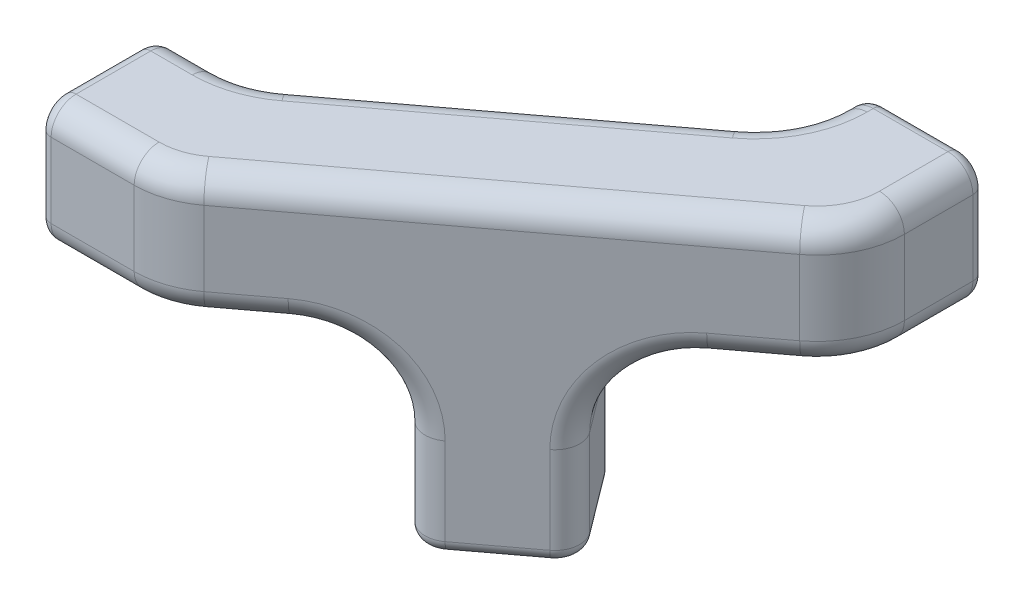
SolidWorks part; units mm, degrees
ref_plane "Front Plane" through (0, 0, 0) normal (0, 0, 1) x (1, 0, 0)
ref_plane "Top Plane" through (0, 0, 0) normal (0, 1, 0) x (1, 0, 0)
ref_plane "Right Plane" through (0, 0, 0) normal (1, 0, 0) x (0, 0, -1)
sketch "Sketch1" plane through (0, 0, 0) normal (0, 1, 0) x (1, 0, 0)
  line L0 (-103.8063, 185.5563) -> (-105.9277, 187.6777) construction
  line L1 (-108.7561, 184.8492) -> (-103.0992, 190.5061)
  line L2 (-103.0992, 190.5061) -> (-100.7186, 188.1255)
  line L3 (-100.7186, 188.1255) -> (-106.3755, 182.4686)
  line L4 (-106.3755, 182.4686) -> (-108.7561, 184.8492)
  line L5 (0, 200) -> (0, -200) construction
  line L6 (118.25, 0) -> (-118.25, 0) construction
  line L7 (100.7186, 188.1255) -> (106.3755, 182.4686)
  line L8 (103.0992, 190.5061) -> (100.7186, 188.1255)
  line L9 (108.7561, 184.8492) -> (103.0992, 190.5061)
  line L10 (106.3755, 182.4686) -> (108.7561, 184.8492)
  line L11 (103.0992, -190.5061) -> (100.7186, -188.1255)
  line L12 (108.7561, -184.8492) -> (103.0992, -190.5061)
  line L13 (106.3755, -182.4686) -> (108.7561, -184.8492)
  line L14 (100.7186, -188.1255) -> (106.3755, -182.4686)
  line L15 (-100.7186, -188.1255) -> (-106.3755, -182.4686)
  line L16 (-103.0992, -190.5061) -> (-100.7186, -188.1255)
  line L17 (-108.7561, -184.8492) -> (-103.0992, -190.5061)
  line L18 (-106.3755, -182.4686) -> (-108.7561, -184.8492)
  arc A0 (-88.25, 192) -> (-110.25, 170) centre (-88.25, 170) ccw construction
  arc A1 (-88.25, 195) -> (-113.25, 170) centre (-88.25, 170) ccw construction
  point P10 (-105.9277, 187.6777)
  point P29 (0, 0)
  point P30 (0, 0)
sketch "Sketch2" plane through (0, 0, 0) normal (0, 1, 0) x (1, 0, 0)
  line L0 (-110.25, 168) -> (-103.5833, 168)
  line L1 (-103.5833, 168) -> (-78.25, 187)
  line L2 (-78.25, 187) -> (-78.25, 192)
  line L3 (-78.25, 192) -> (-88.25, 192) construction
  line L4 (-110.25, 170) -> (-110.25, 168) construction
  line L5 (-110.25, 158) -> (-100.25, 158)
  line L6 (-100.25, 158) -> (-68.25, 182)
  line L7 (-68.25, 182) -> (-68.25, 192)
  line L8 (-68.25, 192) -> (-78.25, 192)
  line L9 (-110.25, 158) -> (-110.25, 168)
  point P7 (-78.25, 192)
  point P12 (-96.4554, 143)
  point P14 (-73.25, 184.0668)
  point P15 (-82.4641, 192)
  point P16 (-86.25, 183.0311)
  dimension "D1" = 2
  dimension "D2" = 10
  dimension "D3" = 10
  dimension "D4" = 10
  dimension "D5" = 10
extrude "Boss-Extrude1" add sketch "Sketch2" along normal blind 10
sketch "Sketch3" plane through (0, 0, 0) normal (0, -1, 0) x (1, 0, 0)
  line L0 (-94.9167, -174.5) -> (-88.9167, -166.5)
  line L1 (-78.25, -187) -> (-103.5833, -168) construction
  line L2 (-100.25, -158) -> (-68.25, -182) construction
  line L3 (-88.9167, -166.5) -> (-80.9167, -172.5)
  line L4 (-80.9167, -172.5) -> (-86.9167, -180.5)
  line L5 (-86.9167, -180.5) -> (-94.9167, -174.5)
  point P6 (-90.9167, -177.5)
  point P9 (-90.9167, -177.5)
  dimension "D1" = 10
extrude "Boss-Extrude2" add sketch "Sketch3" along normal blind 15
sketch "Sketch4" plane through (0, 0, -192) normal (0, 0, -1) x (-1, 0, 0)
  line L0 (68.25, 0) -> (78.25, 10) construction
  circle A0 centre (73.25, 5) radius 2.5
  dimension "D1" = 5
extrude "Cut-Extrude1" cut sketch "Sketch4" against normal blind 10
sketch "Sketch5" plane through (-110.25, 0, 0) normal (-1, 0, 0) x (0, 0, 1)
  line L0 (-158, 10) -> (-158, 0) construction
  line L1 (-168, 10) -> (-158, 10) construction
  circle A0 centre (-163, 5) radius 2.5
  point P4 (-158, 5)
  point P7 (-163, 10)
  dimension "D1" = 5
extrude "Cut-Extrude2" cut sketch "Sketch5" against normal blind 10
sketch "Sketch6" plane through (0, -15, 0) normal (0, -1, 0) x (1, 0, 0)
  line L0 (-94.9167, -174.5) -> (-80.9167, -172.5) construction
  circle A0 centre (-87.9167, -173.5) radius 2.5
  point P6 (0, 0)
  point P7 (-85.8855, -168.6667)
  point P8 (-84.75, -170.6667)
  dimension "D1" = 5
extrude "Cut-Extrude3" cut sketch "Sketch6" against normal blind 10
chamfer "Chamfer1" distance 0.7 angle 45 3 edges at (-75.75, 5, -192) (-110.25, 5, -160.5) (-87.9167, -15, -176)
fillet "Fillet1" radius 7 6 edges at (-68.25, 5, -182) (-78.25, 5, -187) (-103.5833, 5, -168) (-100.25, 5, -158) (-91.9167, 0, -170.5) (-83.9167, 0, -176.5)
fillet "Fillet2" radius 1 12 edges at (-110.25, 5, -158) (-110.25, 10, -163) (-110.25, 5, -168) (-110.25, 0, -163) (-68.25, 5, -192) (-73.25, 10, -192) (-78.25, 5, -192) (-73.25, 0, -192) (-84.9167, -15, -169.5) (-91.9167, -15, -170.5) (-90.9167, -15, -177.5) (-83.9167, -15, -176.5)
fillet "Fillet3" radius 2 42 edges at (-86.9752, -14.7071, -180.0899) (-77.9571, 0.2929, -191.7071) (-68.5429, 0.2929, -191.7071) (-81.3267, -14.7071, -172.5586) (-88.8581, -14.7071, -166.9101) (-109.9571, 0.2929, -158.2929) (-109.9571, 0.2929, -167.7071) (-94.5066, -14.7071, -174.4414) (-109.9571, 9.7071, -167.7071) (-77.9571, 9.7071, -191.7071) (-68.5429, 9.7071, -191.7071) (-109.9571, 9.7071, -158.2929) (-105.9167, 10, -158) (-100.3697, 10, -158.3592) (-84.7167, 10, -169.65) (-68.25, 10, -188.25) (-78.25, 10, -190.75) (-107.5833, 10, -168) (-103.7031, 10, -168.3592) (-91.3833, 10, -177.15) (-94.9167, -10.5, -174.5) (-107.5833, 0, -168) (-103.7031, 0, -168.3592) (-101.1167, 0, -169.85) (-105.9167, 0, -158) (-100.3697, 0, -158.3592) (-96.45, 0, -160.85) (-88.9167, -10.5, -166.5) (-80.9167, -10.5, -172.5) (-68.25, 0, -188.25) (-68.989, 0, -182.3695) (-73.1833, 0, -178.3) (-78.25, 0, -190.75) (-78.989, 0, -187.3695) (-81.1833, 0, -184.8) (-86.9167, -10.5, -180.5) (-68.989, 10, -182.3695) (-78.989, 10, -187.3695) (-96.5569, -2.0503, -173.2698) (-90.5569, -2.0503, -165.2698) (-79.2765, -2.0503, -173.7302) (-85.2765, -2.0503, -181.7302)
